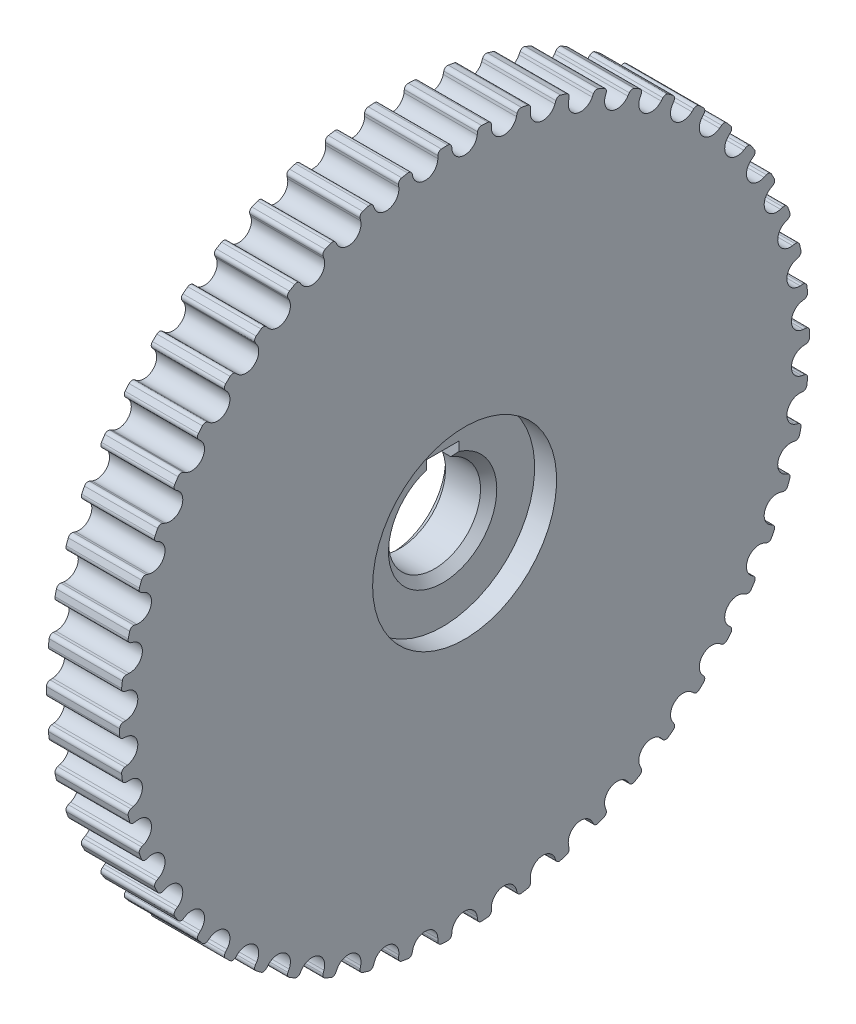
SolidWorks part; units mm, degrees
ref_plane "前视基准面" through (0, 0, 0) normal (0, 0, 1) x (1, 0, 0)
ref_plane "上视基准面" through (0, 0, 0) normal (0, 1, 0) x (1, 0, 0)
ref_plane "右视基准面" through (0, 0, 0) normal (1, 0, 0) x (0, 0, -1)
sketch "草图1" plane through (0, 0, 0) normal (0, 0, 1) x (1, 0, 0)
  line L0 (0, 0) -> (64.8368, 0) construction
  line L1 (0, 5.6538) -> (0, 42.398)
  line L2 (0, 42.398) -> (9, 42.398)
  line L3 (9, 42.398) -> (9, 11.3076)
  line L4 (9, 11.3076) -> (6.3, 11.3076)
  line L5 (6.3, 11.3076) -> (6.3, 5.6538)
  line L6 (6.3, 5.6538) -> (0, 5.6538)
  dimension "L" = 6.3
  dimension "B" = 9
  dimension "d" = 11.3076
  dimension "d1" = 22.6152
  dimension "da" = 84.796
revolve "旋转1" add sketch "草图1" angle 360 about L0
chamfer "倒角1" distance 1 angle 45 2 edges at (6.3, 0, 5.6538) (0, 0, 5.6538)
sketch "草图4" plane through (0, 0, 0) normal (-1, 0, 0) x (0, 0, 1)
  line L1 (-2, 5.2882) -> (2, 5.2882)
  line L2 (-2, 5.2882) -> (-2, 7.4538)
  line L3 (-2, 7.4538) -> (2, 7.4538)
  line L4 (2, 5.2882) -> (2, 7.4538)
  circle A0 centre (0, 0) radius 5.6538 construction
  point P6 (0.2, 7.4538)
  dimension "键槽高度" = 7.4538
  dimension "键槽宽度" = 4
  dimension "t1" = 1.8
extrude "切除-拉伸1" cut sketch "草图4" against normal through all
sketch "草图6" plane through (0, 0, 0) normal (1, 0, 0) x (0, 0, -1)
  line L0 (0, 0) -> (0, 30.6512) construction
  line L1 (1.5874, 41.9257) -> (1.5484, 41.6079)
  line L2 (2.5667, 42.3202) -> (2.7634, 43.9218)
  line L3 (-2.5667, 42.3202) -> (-2.7634, 43.9218)
  line L4 (-1.5874, 41.9257) -> (-1.5484, 41.6079)
  circle A0 centre (0, 0) radius 42.398 construction
  circle A1 centre (0, 0) radius 40.238 construction
  arc A2 (-1.5484, 41.6079) -> (1.5484, 41.6079) centre (0, 41.798) ccw
  arc A3 (2.7634, 43.9218) -> (-2.7634, 43.9218) centre (0, 0) ccw
  arc A4 (1.5874, 41.9257) -> (2.0874, 42.3466) centre (2.0638, 41.8672) cw
  arc A5 (2.0874, 42.3466) -> (2.5667, 42.3202) centre (0, 0) cw
  arc A6 (-2.0874, 42.3466) -> (-2.5667, 42.3202) centre (0, 0) ccw
  arc A7 (-1.5874, 41.9257) -> (-2.0874, 42.3466) centre (-2.0638, 41.8672) ccw
  point P7 (0, 3.25)
  point P8 (0, 28.4912)
  point P15 (1.6415, 42.3662)
  dimension "D1" = 80.476
  dimension "ra" = 0.48
  dimension "rf" = 1.56
  dimension "hg" = 2.16
  dimension "D3" = 0.48
  dimension "D4" = 1.6136
  dimension "angle" = 14
  dimension "bw" = 3.25
extrude "切除-拉伸2" cut sketch "草图6" along normal up to next
ref_axis "基准轴1" through (-1.4, 0, 0) along (1, 0, 0)
pattern_circular "阵列(圆周)3" count 54 over 360 about axis through (-1.4, 0, 0) along (1, 0, 0) of "切除-拉伸2"
equation "\"键槽高度@草图4\" = \"d@草图1\" / 2  + \"t1@草图4\""
equation "\"D1@草图6\" = \"da@草图1\"  - \"hg@草图6\" - \"hg@草图6\""
equation "\"D3@草图6\" = \"ra@草图6\""
